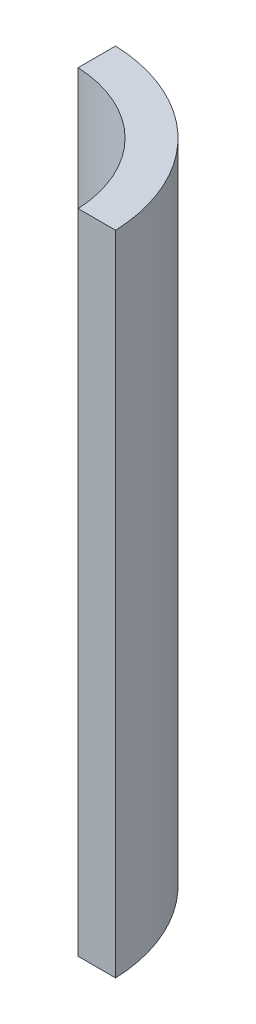
SolidWorks part; units mm, degrees
material "Silicon Rubber"
ref_plane "Front Plane" through (0, 0, 0) normal (0, 0, 1) x (1, 0, 0)
ref_plane "Top Plane" through (0, 0, 0) normal (0, 1, 0) x (1, 0, 0)
ref_plane "Right Plane" through (0, 0, 0) normal (1, 0, 0) x (0, 0, -1)
sketch "Sketch1" plane through (0, 0, 0) normal (0, 1, 0) x (1, 0, 0)
  line L1 (1.5, -37.7202) -> (-1.5, -37.7202)
  line L2 (1.5, -37.7202) -> (1.5, 37.7202)
  line L3 (1.5, 37.7202) -> (-1.5, 37.7202)
  line L4 (-1.5, -37.7202) -> (-1.5, 37.7202)
  line L5 (1.5, -37.7202) -> (-1.5, 37.7202) construction
  line L6 (1.5, 37.7202) -> (-1.5, -37.7202) construction
  line L7 (-37.7202, -1.5) -> (37.7202, -1.5)
  line L8 (-37.7202, -1.5) -> (-37.7202, 1.5)
  line L9 (-37.7202, 1.5) -> (37.7202, 1.5)
  line L10 (37.7202, -1.5) -> (37.7202, 1.5)
  line L11 (-37.7202, -1.5) -> (37.7202, 1.5) construction
  line L12 (-37.7202, 1.5) -> (37.7202, -1.5) construction
  circle A0 centre (0, 0) radius 37.75
  circle A1 centre (0, 0) radius 29.25
  dimension "D1" = 58.5
  dimension "D2" = 75.5
  dimension "D3" = 3
  dimension "D4" = 3
extrude "Boss-Extrude1" add sketch "Sketch1" along normal blind 147 contours A1 L9 A0 L2 region at (21.7026, 0, -21.7026)
